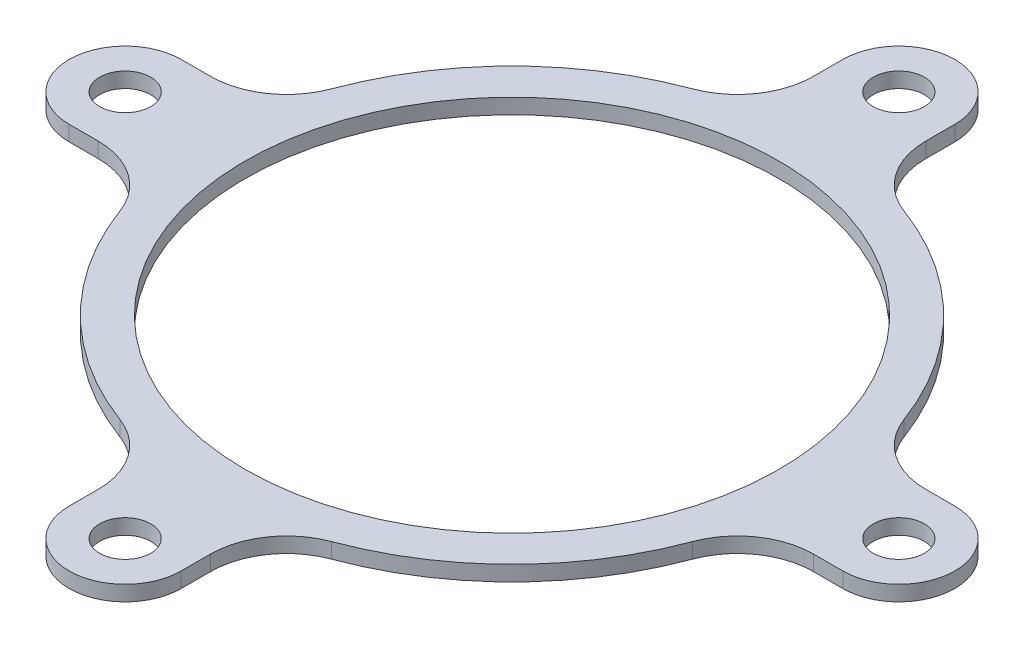
SolidWorks part; units mm, degrees
material "3003 Alloy"
ref_plane "Front Plane" through (0, 0, 0) normal (0, 0, 1) x (1, 0, 0)
ref_plane "Top Plane" through (0, 0, 0) normal (0, 1, 0) x (1, 0, 0)
ref_plane "Right Plane" through (0, 0, 0) normal (1, 0, 0) x (0, 0, -1)
sketch "Sketch1" plane through (0, 0, 0) normal (0, 1, 0) x (1, 0, 0)
  circle A0 centre (0, 0) radius 35
  circle A1 centre (0, 0) radius 40
  dimension "innerDiam" = 70
  dimension "outerDiam" = 80
extrude "Boss-Extrude1" add sketch "Sketch1" along normal mid plane 2
sketch "Sketch2" plane through (0, 1, 0) normal (0, 1, 0) x (1, 0, 0)
  line L0 (0, 0) -> (0, 38.8704) construction
  line L1 (-7.35, 46.8933) -> (-7.35, 50.7)
  line L2 (7.35, 50.7) -> (7.35, 46.8933)
  arc A0 (-7.35, 50.7) -> (7.35, 50.7) centre (0, 50.7) cw
  arc A1 (7.35, 46.8933) -> (13.88, 37.5146) centre (17.35, 46.8933) ccw
  circle A2 centre (0, 0) radius 40 construction
  arc A3 (-7.35, 46.8933) -> (-13.88, 37.5146) centre (-17.35, 46.8933) cw
  arc A4 (13.88, 37.5146) -> (-13.88, 37.5146) centre (0, 0) ccw
  circle A5 centre (0, 0) radius 50.7 construction
  circle A6 centre (0, 50.7) radius 3.35
  dimension "supportsDiam" = 101.4
  dimension "rodDiam" = 6.7
  dimension "D3" = 4
  dimension "D4" = 10
extrude "Boss-Extrude2" add sketch "Sketch2" against normal up to surface (2 mm away) up to face at (0, -1, 40)
pattern_circular "CirPattern1" count 4 over 360 about axis through (0, 1, 0) along (0, -1, 0) of "Boss-Extrude2" reverse direction yes
